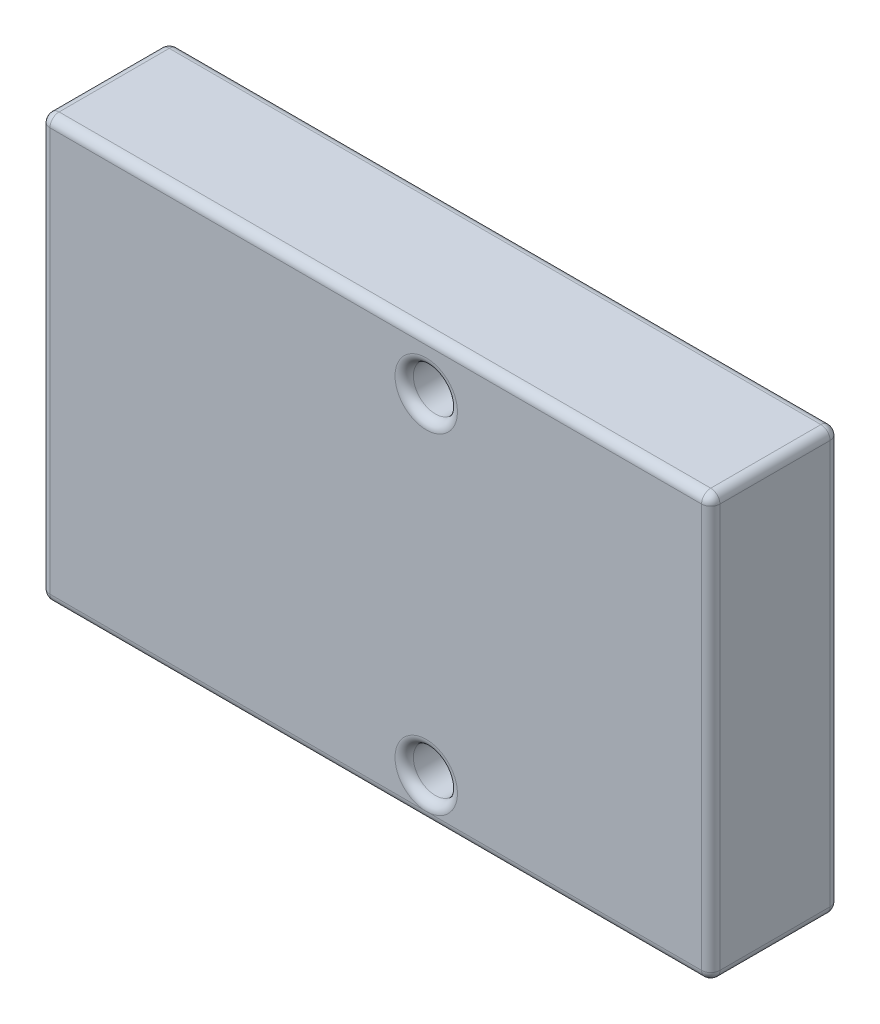
SolidWorks part; units mm, degrees
ref_plane "Front Plane" through (0, 0, 0) normal (0, 0, 1) x (1, 0, 0)
ref_plane "Top Plane" through (0, 0, 0) normal (0, 1, 0) x (1, 0, 0)
ref_plane "Right Plane" through (0, 0, 0) normal (1, 0, 0) x (0, 0, -1)
sketch "Sketch1" plane through (0, 0, 0) normal (0, 1, 0) x (1, 0, 0)
  line L0 (0, 0) -> (36.5, 0)
  line L1 (36.5, 0) -> (36.5, -7)
  line L2 (36.5, -7) -> (0, -7)
  line L3 (0, -7) -> (0, 0)
  dimension "D1" = 36.5
  dimension "D2" = 7
extrude "Boss-Extrude1" add sketch "Sketch1" along normal blind 23
sketch "Sketch2" plane through (0, 0, 0) normal (0, -1, 0) x (1, 0, 0)
  line L0 (36.5, 0) -> (0, 0) construction
  line L1 (36.5, 7) -> (36.5, 0) construction
  line L2 (0, 0) -> (0, 7) construction
  circle A0 centre (8, 3) radius 1.375
  circle A1 centre (28.5, 3) radius 1.375
  dimension "D3" = 2.75
  dimension "D1" = 3
  dimension "D4" = 8
  dimension "D5" = 8
extrude "Cut-Extrude1" cut sketch "Sketch2" against normal blind 8.5
sketch "Sketch4" plane through (0, 0, 0) normal (0, 0, -1) x (-1, 0, 0)
  line L0 (-36.5, 0) -> (0, 0) construction
  line L1 (-28.5, 8.5) -> (-28.5, 0) construction
  circle A0 centre (-21, 2.2) radius 1.2
  circle A1 centre (-21, 20.2) radius 1.2
  dimension "D1" = 2.4
  dimension "D4" = 18
  dimension "D2" = 2.2
  dimension "D3" = 7.5
extrude "Cut-Extrude2" cut sketch "Sketch4" against normal blind 7
fillet "Fillet1" radius 0.5 18 edges at (18.25, 23, 0) (19.8, 20.2, 0) (19.8, 2.2, 0) (0, 11.5, 0) (0, 23, 3.5) (36.5, 23, 3.5) (36.5, 11.5, 0) (0, 11.5, 7) (18.25, 23, 7) (36.5, 11.5, 7) (19.8, 20.2, 7) (19.8, 2.2, 7) (18.25, 0, 7) (36.5, 0, 3.5) (18.25, 0, 0) (0, 0, 3.5) (28.5, 0, 1.625) (8, 0, 1.625)
